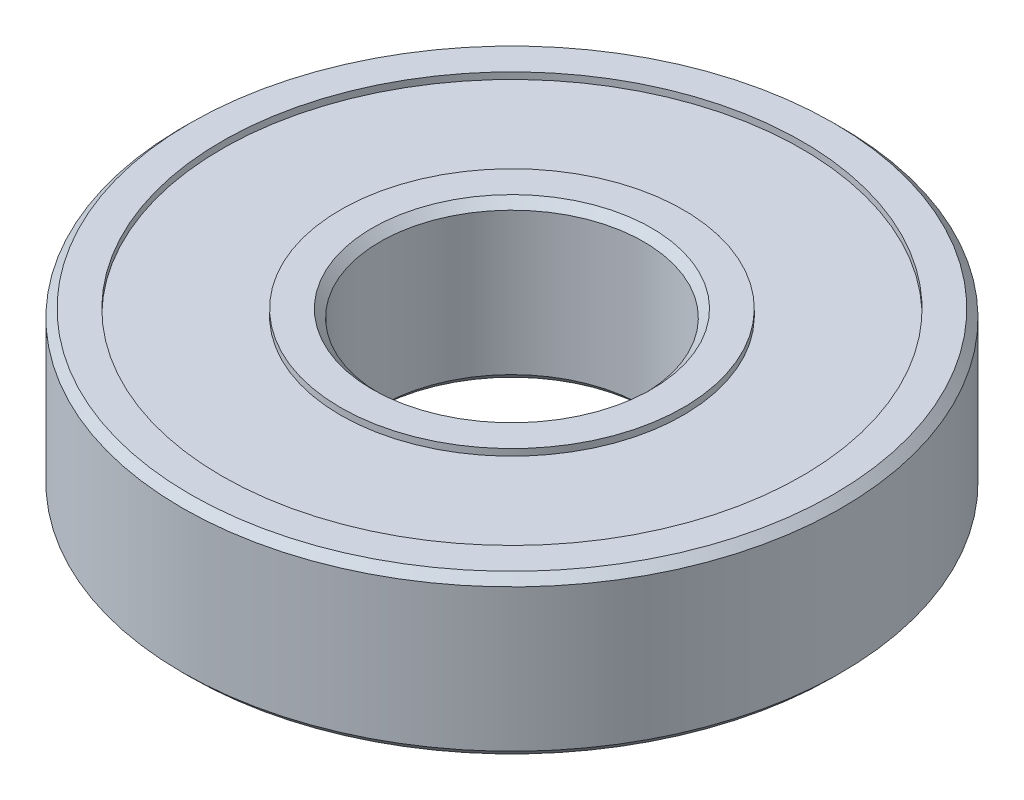
SolidWorks part; units mm, degrees
ref_plane "Front Plane" through (0, 0, 0) normal (0, 0, 1) x (1, 0, 0)
ref_plane "Top Plane" through (0, 0, 0) normal (0, 1, 0) x (1, 0, 0)
ref_plane "Right Plane" through (0, 0, 0) normal (1, 0, 0) x (0, 0, -1)
sketch "Sketch1" plane through (0, 0, 0) normal (0, 1, 0) x (1, 0, 0)
  circle A0 centre (0, 0) radius 5
  circle A1 centre (0, 0) radius 11
  circle A3 centre (0, 0) radius 12.5
  circle A4 centre (0, 0) radius 6.5
  dimension "D1" = 10
  dimension "D2" = 22
  dimension "D3" = 1.5
  dimension "D4" = 1.5
extrude "Boss-Extrude1" add sketch "Sketch1" along normal mid plane 5.5 contours A1 A4 region at (-10.6889, 0, 0)
extrude "Boss-Extrude2" add sketch "Sketch1<3>" along normal mid plane 6 contours A3 A1 | A4 A0 region at (-12.1464, 0, 0) region at (-6.3162, 0, 0)
sketch "Sketch1<3>" plane through (0, 0, 0) normal (0, 1, 0) x (1, 0, 0) same geometry as "Sketch1"
chamfer "Chamfer1" distance 0.3 angle 45 4 edges at (0, -3, 5) (0, 3, 5) (0, -3, 12.5) (0, 3, 12.5)
